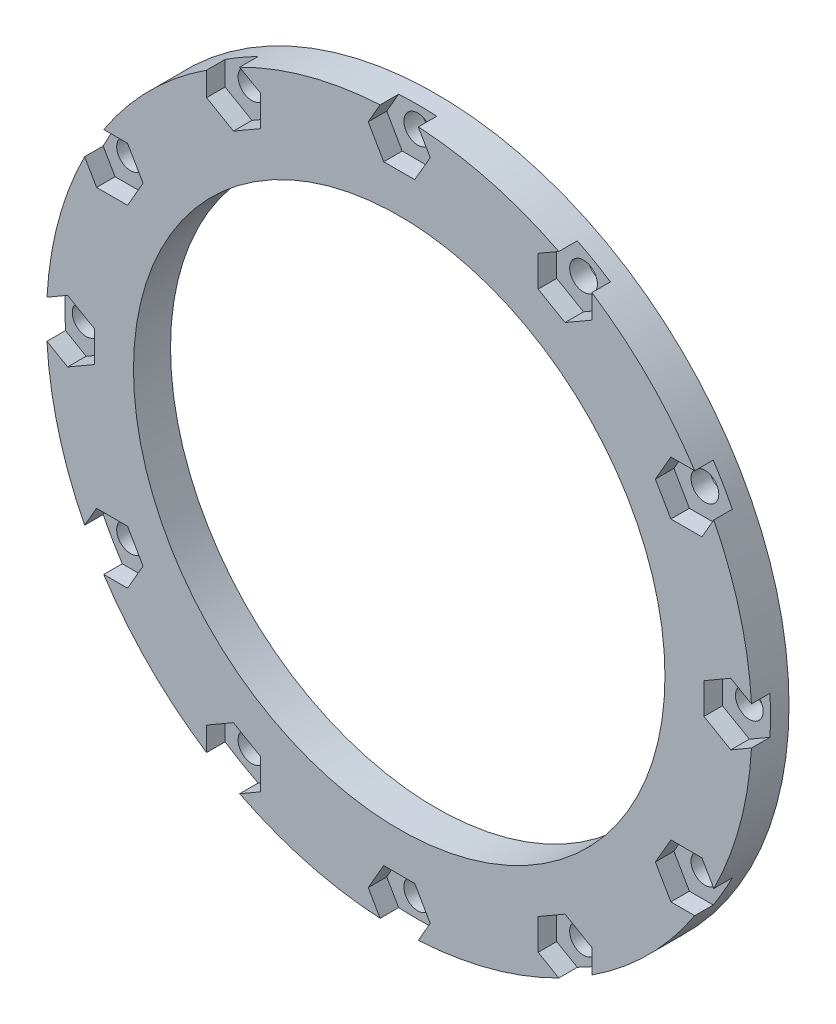
SolidWorks part; units mm, degrees
ref_plane "Front Plane" through (0, 0, 0) normal (0, 0, 1) x (1, 0, 0)
ref_plane "Top Plane" through (0, 0, 0) normal (0, 1, 0) x (1, 0, 0)
ref_plane "Right Plane" through (0, 0, 0) normal (1, 0, 0) x (0, 0, -1)
sketch "Sketch1" plane through (0, 0, 0) normal (0, 0, 1) x (1, 0, 0)
  circle A0 centre (0, 0) radius 38.1
  circle A1 centre (0, 0) radius 28.702
  dimension "D1" = 76.2
  dimension "D2" = 57.404
extrude "Boss-Extrude1" add sketch "Sketch1" along normal blind 4
sketch "Sketch2" plane through (0, 0, 4) normal (0, 0, 1) x (1, 0, 0)
  line L0 (0, 0) -> (0, 44.3901) construction
  circle A0 centre (0, 0) radius 35.814 construction
  circle A1 centre (0, 35.814) radius 1.5
  circle A2 centre (17.907, 31.0158) radius 1.5
  circle A3 centre (31.0158, 17.907) radius 1.5
  circle A4 centre (35.814, 0) radius 1.5
  circle A5 centre (31.0158, -17.907) radius 1.5
  circle A6 centre (17.907, -31.0158) radius 1.5
  circle A7 centre (0, -35.814) radius 1.5
  circle A8 centre (-17.907, -31.0158) radius 1.5
  circle A9 centre (-31.0158, -17.907) radius 1.5
  circle A10 centre (-35.814, 0) radius 1.5
  circle A11 centre (-31.0158, 17.907) radius 1.5
  circle A12 centre (-17.907, 31.0158) radius 1.5
  point P30 (0, 0)
  dimension "D1" = 71.628
  dimension "D2" = 3
  dimension "D3" = 12
extrude "Cut-Extrude1" cut sketch "Sketch2" against normal through all
sketch "Sketch4" plane through (0, 0, 4) normal (0, 0, 1) x (1, 0, 0)
  line L0 (0, 0) -> (0, 44.4924) construction
  line L1 (0, 35.814) -> (3.4817, 35.814) construction
  line L2 (20.807, 29.3415) -> (20.807, 32.6901)
  line L3 (3.3486, 35.814) -> (1.6743, 38.714)
  line L4 (1.6743, 38.714) -> (-1.6743, 38.714)
  line L5 (-1.6743, 38.714) -> (-3.3486, 35.814)
  line L6 (-3.3486, 35.814) -> (-1.6743, 32.914)
  line L7 (-1.6743, 32.914) -> (1.6743, 32.914)
  line L8 (1.6743, 32.914) -> (3.3486, 35.814)
  line L9 (20.807, 32.6901) -> (17.907, 34.3645)
  line L10 (17.907, 34.3645) -> (15.007, 32.6901)
  line L11 (15.007, 32.6901) -> (15.007, 29.3415)
  line L12 (15.007, 29.3415) -> (17.907, 27.6672)
  line L13 (17.907, 27.6672) -> (20.807, 29.3415)
  line L14 (17.907, 31.0158) -> (20.9222, 29.275) construction
  line L15 (32.6901, 15.007) -> (34.3645, 17.907)
  line L16 (34.3645, 17.907) -> (32.6901, 20.807)
  line L17 (32.6901, 20.807) -> (29.3415, 20.807)
  line L18 (29.3415, 20.807) -> (27.6672, 17.907)
  line L19 (27.6672, 17.907) -> (29.3415, 15.007)
  line L20 (29.3415, 15.007) -> (32.6901, 15.007)
  line L21 (31.0158, 17.907) -> (32.7567, 14.8918) construction
  line L22 (35.814, -3.3486) -> (38.714, -1.6743)
  line L23 (38.714, -1.6743) -> (38.714, 1.6743)
  line L24 (38.714, 1.6743) -> (35.814, 3.3486)
  line L25 (35.814, 3.3486) -> (32.914, 1.6743)
  line L26 (32.914, 1.6743) -> (32.914, -1.6743)
  line L27 (32.914, -1.6743) -> (35.814, -3.3486)
  line L28 (35.814, 0) -> (35.814, -3.4817) construction
  line L29 (29.3415, -20.807) -> (32.6901, -20.807)
  line L30 (32.6901, -20.807) -> (34.3645, -17.907)
  line L31 (34.3645, -17.907) -> (32.6901, -15.007)
  line L32 (32.6901, -15.007) -> (29.3415, -15.007)
  line L33 (29.3415, -15.007) -> (27.6672, -17.907)
  line L34 (27.6672, -17.907) -> (29.3415, -20.807)
  line L35 (31.0158, -17.907) -> (29.275, -20.9222) construction
  line L36 (15.007, -32.6901) -> (17.907, -34.3645)
  line L37 (17.907, -34.3645) -> (20.807, -32.6901)
  line L38 (20.807, -32.6901) -> (20.807, -29.3415)
  line L39 (20.807, -29.3415) -> (17.907, -27.6672)
  line L40 (17.907, -27.6672) -> (15.007, -29.3415)
  line L41 (15.007, -29.3415) -> (15.007, -32.6901)
  line L42 (17.907, -31.0158) -> (14.8918, -32.7567) construction
  line L43 (-3.3486, -35.814) -> (-1.6743, -38.714)
  line L44 (-1.6743, -38.714) -> (1.6743, -38.714)
  line L45 (1.6743, -38.714) -> (3.3486, -35.814)
  line L46 (3.3486, -35.814) -> (1.6743, -32.914)
  line L47 (1.6743, -32.914) -> (-1.6743, -32.914)
  line L48 (-1.6743, -32.914) -> (-3.3486, -35.814)
  line L49 (0, -35.814) -> (-3.4817, -35.814) construction
  line L50 (-20.807, -29.3415) -> (-20.807, -32.6901)
  line L51 (-20.807, -32.6901) -> (-17.907, -34.3645)
  line L52 (-17.907, -34.3645) -> (-15.007, -32.6901)
  line L53 (-15.007, -32.6901) -> (-15.007, -29.3415)
  line L54 (-15.007, -29.3415) -> (-17.907, -27.6672)
  line L55 (-17.907, -27.6672) -> (-20.807, -29.3415)
  line L56 (-17.907, -31.0158) -> (-20.9222, -29.275) construction
  line L57 (-32.6901, -15.007) -> (-34.3645, -17.907)
  line L58 (-34.3645, -17.907) -> (-32.6901, -20.807)
  line L59 (-32.6901, -20.807) -> (-29.3415, -20.807)
  line L60 (-29.3415, -20.807) -> (-27.6672, -17.907)
  line L61 (-27.6672, -17.907) -> (-29.3415, -15.007)
  line L62 (-29.3415, -15.007) -> (-32.6901, -15.007)
  line L63 (-31.0158, -17.907) -> (-32.7567, -14.8918) construction
  line L64 (-35.814, 3.3486) -> (-38.714, 1.6743)
  line L65 (-38.714, 1.6743) -> (-38.714, -1.6743)
  line L66 (-38.714, -1.6743) -> (-35.814, -3.3486)
  line L67 (-35.814, -3.3486) -> (-32.914, -1.6743)
  line L68 (-32.914, -1.6743) -> (-32.914, 1.6743)
  line L69 (-32.914, 1.6743) -> (-35.814, 3.3486)
  line L70 (-35.814, 0) -> (-35.814, 3.4817) construction
  line L71 (-29.3415, 20.807) -> (-32.6901, 20.807)
  line L72 (-32.6901, 20.807) -> (-34.3645, 17.907)
  line L73 (-34.3645, 17.907) -> (-32.6901, 15.007)
  line L74 (-32.6901, 15.007) -> (-29.3415, 15.007)
  line L75 (-29.3415, 15.007) -> (-27.6672, 17.907)
  line L76 (-27.6672, 17.907) -> (-29.3415, 20.807)
  line L77 (-31.0158, 17.907) -> (-29.275, 20.9222) construction
  line L78 (-15.007, 32.6901) -> (-17.907, 34.3645)
  line L79 (-17.907, 34.3645) -> (-20.807, 32.6901)
  line L80 (-20.807, 32.6901) -> (-20.807, 29.3415)
  line L81 (-20.807, 29.3415) -> (-17.907, 27.6672)
  line L82 (-17.907, 27.6672) -> (-15.007, 29.3415)
  line L83 (-15.007, 29.3415) -> (-15.007, 32.6901)
  line L84 (-17.907, 31.0158) -> (-14.8918, 32.7567) construction
  circle A0 centre (0, 35.814) radius 2.9 construction
  circle A1 centre (17.907, 31.0158) radius 2.9 construction
  circle A2 centre (31.0158, 17.907) radius 2.9 construction
  circle A3 centre (35.814, 0) radius 2.9 construction
  circle A4 centre (31.0158, -17.907) radius 2.9 construction
  circle A5 centre (17.907, -31.0158) radius 2.9 construction
  circle A6 centre (0, -35.814) radius 2.9 construction
  circle A7 centre (-17.907, -31.0158) radius 2.9 construction
  circle A8 centre (-31.0158, -17.907) radius 2.9 construction
  circle A9 centre (-35.814, 0) radius 2.9 construction
  circle A10 centre (-31.0158, 17.907) radius 2.9 construction
  circle A11 centre (-17.907, 31.0158) radius 2.9 construction
  point P115 (0, 0)
  dimension "D1" = 5.8
  dimension "D2" = 12
extrude "Cut-Extrude3" cut sketch "Sketch4" against normal blind 2
